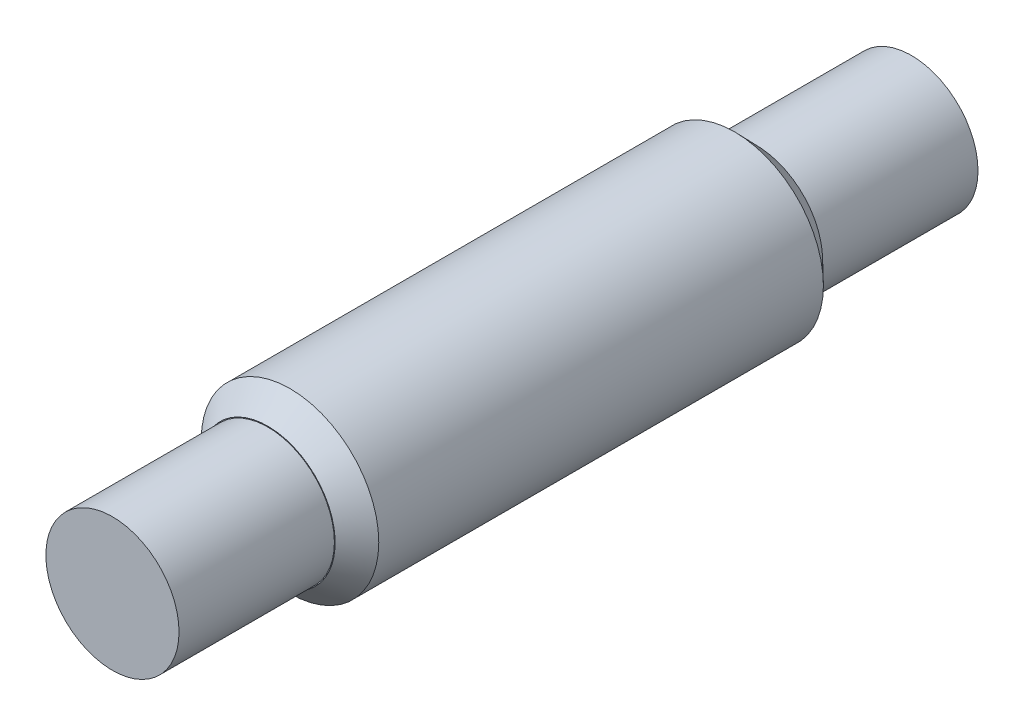
SolidWorks part; units mm, degrees
ref_plane "Front Plane" through (0, 0, 0) normal (0, 0, 1) x (1, 0, 0)
ref_plane "Top Plane" through (0, 0, 0) normal (0, 1, 0) x (1, 0, 0)
ref_plane "Right Plane" through (0, 0, 0) normal (1, 0, 0) x (0, 0, -1)
sketch "Sketch1" plane through (0, 0, 0) normal (1, 0, 0) x (0, 0, -1)
  line L0 (55, 0) -> (-55, 0) construction
  line L1 (-9, 0) -> (9, 0)
  line L2 (-9, 0) -> (-9, 1.5)
  line L3 (-9, 1.5) -> (-5.5, 1.5)
  line L4 (9, 0) -> (9, 1.5)
  line L5 (0, 0) -> (0, 1.5) construction
  line L6 (-5.5, 1.5) -> (-5.5, 2)
  line L7 (-5.5, 2) -> (5.5, 2)
  line L8 (5.5, 2) -> (5.5, 1.5)
  line L9 (5.5, 1.5) -> (9, 1.5)
  dimension "D1" = 18
  dimension "D2" = 1.5
  dimension "D3" = 3.5
  dimension "D4" = 2
revolve "Revolve1" add sketch "Sketch1" angle 360 about L1
chamfer "Chamfer1" distance 0.5 angle 44 2 edges at (2, 0, -5.5) (2, 0, 5.5) first distance on face at (2, 0, -5.5) first distance on face at (2, 0, 5.5)
